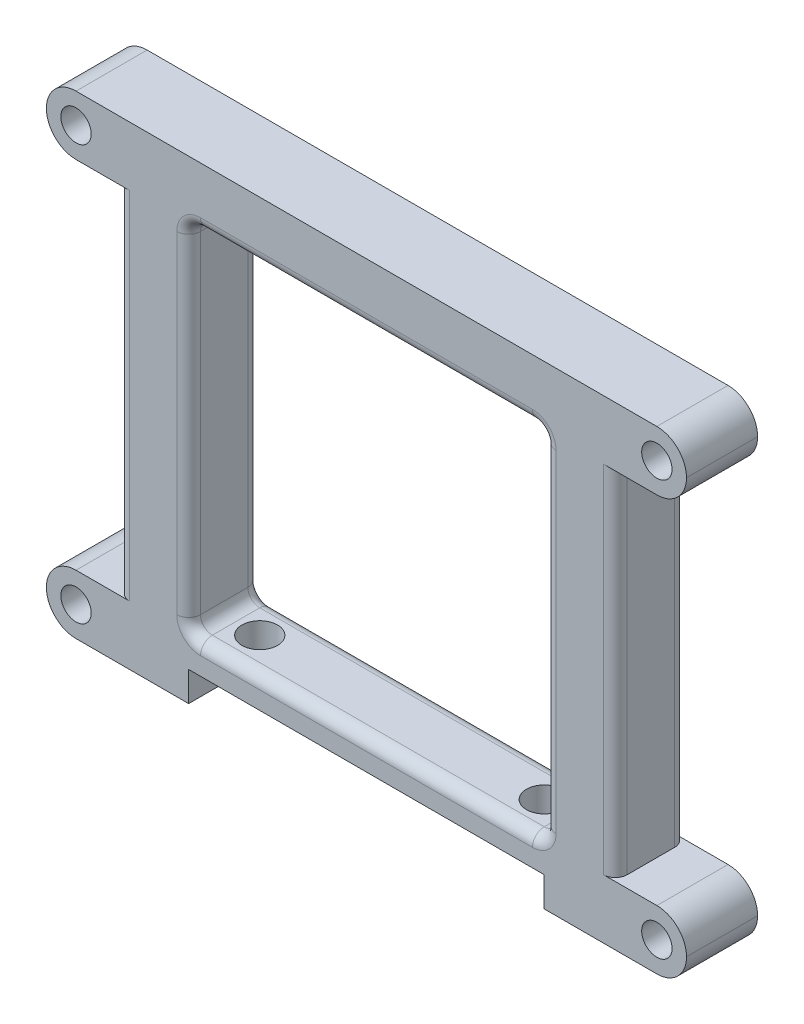
SolidWorks part; units mm, degrees
ref_plane "Front Plane" through (0, 0, 0) normal (0, 0, 1) x (1, 0, 0)
ref_plane "Top Plane" through (0, 0, 0) normal (0, 1, 0) x (1, 0, 0)
ref_plane "Right Plane" through (0, 0, 0) normal (1, 0, 0) x (0, 0, -1)
sketch "Sketch3" plane through (0, 0, 0) normal (0, 0, 1) x (1, 0, 0)
  line L0 (-26.67, 22.225) -> (0, 22.225) construction
  line L1 (34.29, -3.175) -> (-34.29, -3.175) construction
  line L2 (34.29, -3.175) -> (34.29, 3.175)
  line L3 (34.29, 3.175) -> (26.67, 3.175)
  line L4 (-34.29, -3.175) -> (-34.29, 3.175)
  line L5 (34.29, -3.175) -> (-34.29, 3.175) construction
  line L6 (34.29, 3.175) -> (-34.29, -3.175) construction
  line L8 (-26.67, 3.175) -> (-26.67, 41.275)
  line L10 (-19.05, 3.175) -> (-19.05, 41.275)
  line L11 (0, -55) -> (0, 55) construction
  line L12 (-26.67, 3.175) -> (-34.29, 3.175)
  line L13 (34.29, 47.625) -> (34.29, 41.275)
  line L14 (34.29, 47.625) -> (-34.29, 47.625)
  line L15 (-34.29, 47.625) -> (-34.29, 41.275)
  line L16 (-26.67, 41.275) -> (-34.29, 41.275)
  line L17 (34.29, 41.275) -> (26.67, 41.275)
  line L18 (26.67, 3.175) -> (26.67, 41.275)
  line L19 (19.05, 3.175) -> (19.05, 41.275)
  line L20 (19.05, 41.275) -> (-19.05, 41.275)
  line L21 (19.05, 3.175) -> (-19.05, 3.175)
  line L24 (-19.05, -3.175) -> (-34.29, -3.175)
  line L26 (19.05, -3.175) -> (34.29, -3.175)
  line L27 (-19.05, 0) -> (19.05, 0)
  line L28 (-19.05, 0) -> (-19.05, -3.175)
  line L29 (19.05, 0) -> (19.05, -3.175)
  point P0 (0, 0)
  dimension "D1" = 6.35
  dimension "D2" = 68.58
  dimension "D3" = 7.62
  dimension "D4" = 7.62
  dimension "D5" = 38.1
  dimension "D6" = 3.175
extrude "Boss-Extrude2" add sketch "Sketch3" along normal mid plane 7.62
fillet "Fillet1" radius 3.175 8 edges at (34.29, 3.175, 0) (34.29, 41.275, 0) (34.29, 47.625, 0) (-34.29, 3.175, 0) (-34.29, 41.275, 0) (-34.29, 47.625, 0) (34.29, -3.175, 0) (-34.29, -3.175, 0)
sketch "Sketch4" plane through (0, 0, 3.81) normal (0, 0, 1) x (1, 0, 0)
  circle A0 centre (-31.115, 44.45) radius 1.627
  circle A1 centre (-31.115, 0) radius 1.627
  dimension "D1" = 3.254
  dimension "D2" = 3.254
extrude "Cut-Extrude1" cut sketch "Sketch4" against normal up to next
mirror "Mirror1" about plane through (0, 0, 0) normal (1, 0, 0) of "Cut-Extrude1"
fillet "Fillet2" radius 1.27 16 edges at (0, 3.175, 3.81) (0, 3.175, -3.81) (0, 41.275, 3.81) (0, 41.275, -3.81) (19.05, 41.275, 0) (19.05, 22.225, 3.81) (19.05, 3.175, 0) (19.05, 22.225, -3.81) (-19.05, 3.175, 0) (-19.05, 22.225, 3.81) (-19.05, 41.275, 0) (-19.05, 22.225, -3.81) (26.67, 22.225, 3.81) (26.67, 22.225, -3.81) (-26.67, 22.225, -3.81) (-26.67, 22.225, 3.81)
sketch "Sketch5" plane through (0, 0, 0) normal (0, -1, 0) x (1, 0, 0)
  line L0 (0, 3.81) -> (0, -3.81) construction
  line L1 (-19.05, 3.81) -> (19.05, 3.81) construction
  line L2 (-19.05, -3.81) -> (19.05, -3.81) construction
  circle A0 centre (-15.24, 0) radius 1.905
  circle A1 centre (15.24, 0) radius 1.905
  dimension "D1" = 3.81
  dimension "D2" = 15.24
extrude "Cut-Extrude2" cut sketch "Sketch5" against normal up to next
